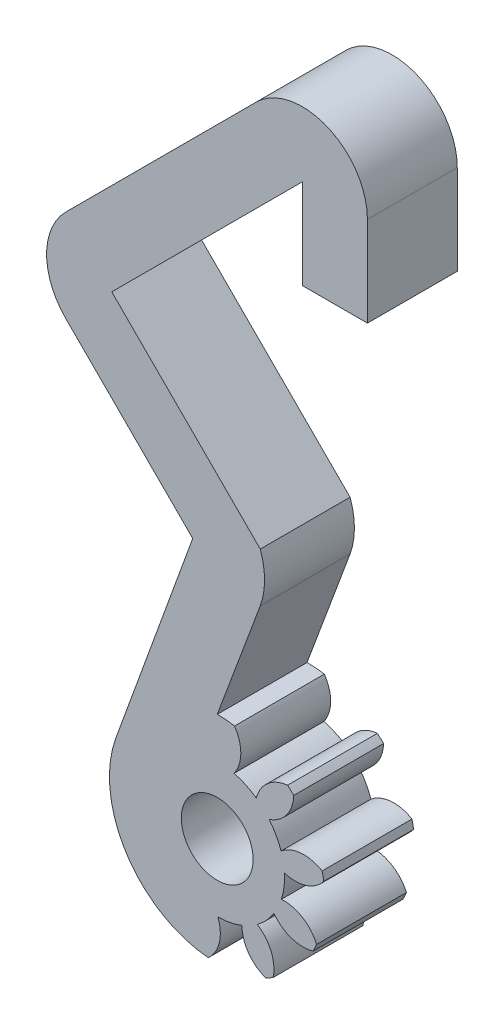
SolidWorks part; units mm, degrees
ref_plane "Ön Düzlem" through (0, 0, 0) normal (0, 0, 1) x (1, 0, 0)
ref_plane "Üst Düzlem" through (0, 0, 0) normal (0, 1, 0) x (1, 0, 0)
ref_plane "Sağ Düzlem" through (0, 0, 0) normal (1, 0, 0) x (0, 0, -1)
sketch "Sketch1" plane through (0, 0, 0) normal (0, 0, 1) x (1, 0, 0)
  line L0 (-2.5201, 10.0188) -> (-2.5201, 12.2698)
  line L1 (-2.5201, 12.2698) -> (-0.1242, 18.7)
  line L2 (-3.883, 20.0681) -> (-8.1583, 8.322)
  line L3 (-3.883, 20.0681) -> (-10.9541, 27.1392)
  line L4 (-8.3907, 29.7026) -> (-0.1242, 21.4362)
  line L6 (-8.3907, 29.7026) -> (2.2159, 40.3092)
  line L9 (2.2159, 40.3092) -> (2.2159, 35.3092)
  line L10 (2.2159, 35.3092) -> (5.8412, 35.3092)
  line L13 (5.8412, 35.3092) -> (5.8412, 40.3092)
  line L14 (-0.3475, 42.8726) -> (-10.9541, 32.266)
  arc A0 (-8.1583, 8.322) -> (-2.5201, 12.2698) centre (-2.5201, 6.2698) ccw
  circle A1 centre (-2.5201, 6.2698) radius 2
  circle A2 centre (-2.5201, 6.2698) radius 3.749
  arc A3 (-10.9541, 32.266) -> (-10.9541, 27.1392) centre (-8.3907, 29.7026) ccw
  arc A5 (-0.1242, 18.7) -> (-0.1242, 21.4362) centre (-3.883, 20.0681) ccw
  arc A7 (-0.3475, 42.8726) -> (5.8412, 40.3092) centre (2.2159, 40.3092) cw
extrude "Boss-Extrude1" add sketch "Sketch1" along normal blind 5 contours A0 L2 L3 A3 L14 A7 L13 L10 L9 L6 L4 A5 L1
extrude "Cut-Extrude1" cut sketch "Sketch1<4>" along normal up to next contours A1 region at (-2.5201, 6.2698, 0)
sketch "Sketch1<4>" plane through (0, 0, 0) normal (0, 0, 1) x (1, 0, 0) same geometry as "Sketch1"
sketch "Sketch3" plane through (0, 0, 0) normal (0, 0, 1) x (1, 0, 0)
  arc A80 (3.3203, 7.6443) -> (1.0344, 7.4616) centre (2.3079, 5.9194) ccw
  arc A81 (1.0344, 7.4616) -> (0.3742, 8.6527) centre (-2.5201, 6.2698) ccw
  arc A82 (0.3742, 8.6527) -> (1.7404, 10.4945) centre (-0.2588, 10.5499) ccw
  arc A83 (1.7404, 10.4945) -> (1.397, 10.8147) centre (-2.5201, 6.2698) ccw
  arc A84 (1.397, 10.8147) -> (-0.3449, 9.3233) centre (1.5918, 8.8242) ccw
  arc A85 (-0.3449, 9.3233) -> (-1.5792, 9.8988) centre (-2.5201, 6.2698) ccw
  arc A86 (-1.5792, 9.8988) -> (-1.5564, 12.1919) centre (-3.2064, 11.0617) ccw
  arc A87 (-1.5564, 12.1919) -> (-2.0225, 12.2492) centre (-2.5201, 6.2698) ccw
  arc A88 (-2.0225, 12.2492) -> (-2.5551, 10.0187) centre (-0.6949, 10.7533) ccw
  arc A89 (-2.5551, 10.0187) -> (-3.892, 9.7588) centre (-2.5201, 6.2698) ccw
  arc A90 (-3.892, 9.7588) -> (-5.2214, 11.6273) centre (-5.8919, 9.7431) ccw
  arc A91 (-5.2214, 11.6273) -> (-5.6321, 11.3997) centre (-2.5201, 6.2698) ccw
  arc A92 (-5.6321, 11.3997) -> (-4.7519, 9.2821) centre (-3.6788, 10.9698) ccw
  arc A93 (-4.7519, 9.2821) -> (-5.6808, 8.2861) centre (-2.5201, 6.2698) ccw
  arc A94 (-5.6808, 8.2861) -> (-7.8546, 9.0164) centre (-7.2895, 7.0979) ccw
  arc A95 (-7.8546, 9.0164) -> (-8.053, 8.5908) centre (-2.5201, 6.2698) ccw
  arc A96 (-8.053, 8.5908) -> (-6.0963, 7.395) centre (-6.2201, 9.3912) ccw
  arc A97 (-6.0963, 7.395) -> (-6.2623, 6.0432) centre (-2.5201, 6.2698) ccw
  arc A98 (-6.2623, 6.0432) -> (-8.4502, 5.3563) centre (-6.8653, 4.1363) ccw
  arc A99 (-8.4502, 5.3563) -> (-8.3606, 4.8954) centre (-2.5201, 6.2698) ccw
  arc A100 (-8.3606, 4.8954) -> (-6.0747, 5.0781) centre (-7.3482, 6.6202) ccw
  arc A101 (-6.0747, 5.0781) -> (-5.4144, 3.8869) centre (-2.5201, 6.2698) ccw
  arc A102 (-5.4144, 3.8869) -> (-6.7807, 2.0452) centre (-4.7814, 1.9897) ccw
  arc A103 (-6.7807, 2.0452) -> (-6.4373, 1.725) centre (-2.5201, 6.2698) ccw
  arc A104 (-6.4373, 1.725) -> (-4.6953, 3.2164) centre (-6.632, 3.7155) ccw
  arc A105 (-4.6953, 3.2164) -> (-3.461, 2.6408) centre (-2.5201, 6.2698) ccw
  arc A106 (-3.461, 2.6408) -> (-3.4838, 0.3477) centre (-1.8338, 1.478) ccw
  arc A107 (-3.4838, 0.3477) -> (-3.0178, 0.2905) centre (-2.5201, 6.2698) ccw
  arc A108 (-3.0178, 0.2905) -> (-2.4851, 2.521) centre (-4.3453, 1.7864) ccw
  arc A109 (-2.4851, 2.521) -> (-1.1482, 2.7809) centre (-2.5201, 6.2698) ccw
  arc A110 (-1.1482, 2.7809) -> (0.1812, 0.9123) centre (0.8517, 2.7966) ccw
  arc A111 (0.1812, 0.9123) -> (0.5918, 1.1399) centre (-2.5201, 6.2698) ccw
  arc A112 (0.5918, 1.1399) -> (-0.2883, 3.2575) centre (-1.3614, 1.5698) ccw
  arc A113 (-0.2883, 3.2575) -> (0.6405, 4.2536) centre (-2.5201, 6.2698) ccw
  arc A114 (0.6405, 4.2536) -> (2.8144, 3.5233) centre (2.2493, 5.4418) ccw
  arc A115 (2.8144, 3.5233) -> (3.0128, 3.9488) centre (-2.5201, 6.2698) ccw
  arc A116 (3.0128, 3.9488) -> (1.0561, 5.1447) centre (1.1799, 3.1485) ccw
  arc A117 (1.0561, 5.1447) -> (1.222, 6.4964) centre (-2.5201, 6.2698) ccw
  arc A118 (1.222, 6.4964) -> (3.4099, 7.1834) centre (1.8251, 8.4033) ccw
  arc A119 (3.4099, 7.1834) -> (3.3203, 7.6443) centre (-2.5201, 6.2698) ccw
  point P1 (0, 0)
sketch "Sketch5" plane through (0, 0, 0) normal (0, 0, -1) x (-1, 0, 0)
  line L0 (2.0225, 12.2492) -> (2.2092, 10.0059)
  line L1 (2.8311, 2.5337) -> (3.0178, 0.2905)
  arc A0 (2.2092, 10.0059) -> (2.8311, 2.5337) centre (2.5201, 6.2698) ccw
  arc A1 (2.0225, 12.2492) -> (3.0178, 0.2905) centre (2.5201, 6.2698) ccw
extrude "Cut-Extrude2" cut sketch "Sketch5" against normal blind 5
extrude "Boss-Extrude2" add sketch "Sketch3" along normal blind 5
sketch "Sketch6" plane through (0, 0, 0) normal (0, 0, -1) x (-1, 0, 0)
  circle A0 centre (2.5201, 6.2698) radius 2
extrude "Cut-Extrude3" cut sketch "Sketch6" against normal blind 5
